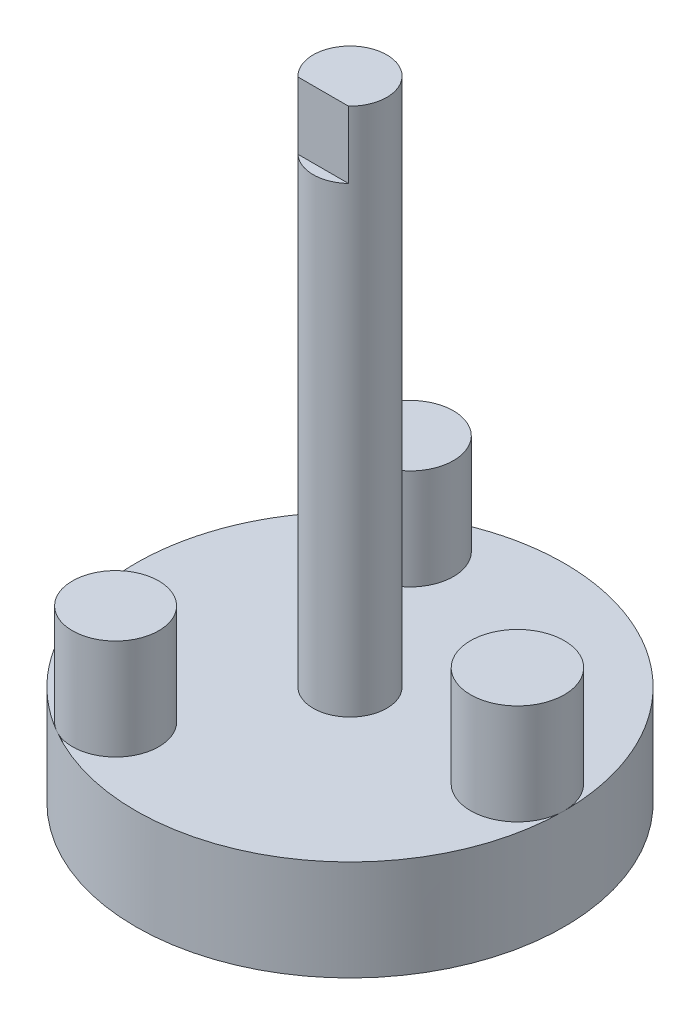
SolidWorks part; units mm, degrees
ref_plane "Front Plane" through (0, 0, 0) normal (0, 0, 1) x (1, 0, 0)
ref_plane "Top Plane" through (0, 0, 0) normal (0, 1, 0) x (1, 0, 0)
ref_plane "Right Plane" through (0, 0, 0) normal (1, 0, 0) x (0, 0, -1)
sketch "Sketch1" plane through (0, 0, 0) normal (0, 1, 0) x (1, 0, 0)
  circle A0 centre (0, 0) radius 32
  dimension "D1" = 64
extrude "Boss-Extrude1" add sketch "Sketch1" along normal blind 15
sketch "Sketch2" plane through (0, 15, 0) normal (0, 1, 0) x (1, 0, 0)
  circle A4 centre (25, 0) radius 7
  circle A5 centre (-13, 22) radius 6.4461
  circle A6 centre (-13, -22) radius 6.4461
extrude "Boss-Extrude2" add sketch "Sketch2" along normal blind 15
sketch "Sketch3" plane through (0, 15, 0) normal (0, 1, 0) x (1, 0, 0)
  circle A0 centre (0, 0) radius 5.5
  dimension "D1" = 11
extrude "Boss-Extrude3" add sketch "Sketch3" along normal blind 79
sketch "Sketch4" plane through (0, 0, 0) normal (1, 0, 0) x (0, 0, -1)
  line L1 (5.5, 94) -> (-5.5, 94) construction
  line L3 (-4.5, 84) -> (-8.7576, 84)
  line L4 (-8.7576, 84) -> (-8.7576, 94)
  line L5 (-8.7576, 94) -> (-4.5, 94)
  line L6 (-4.5, 94) -> (-4, 94)
  line L7 (-4, 94) -> (-4, 84)
  line L8 (-4, 84) -> (-4.5, 84)
  dimension "D2" = 10
extrude "Cut-Extrude1" cut sketch "Sketch4" against normal blind 79 and the other way blind 79
